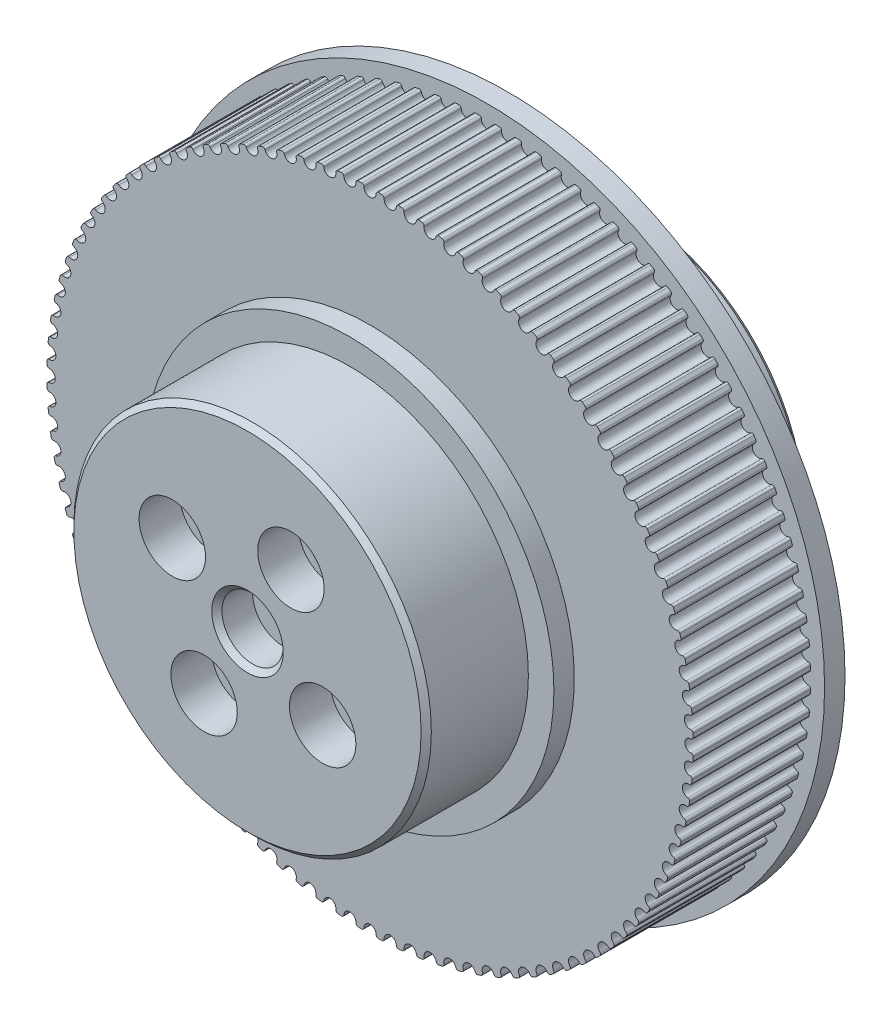
SolidWorks part; units mm, degrees
note: '?' marks a value the reader was unsure of.
ref_plane "Спереди" through (0, 0, 0) normal (0, 0, 1) x (1, 0, 0)
ref_plane "Сверху" through (0, 0, 0) normal (0, 1, 0) x (1, 0, 0)
ref_plane "Справа" through (0, 0, 0) normal (1, 0, 0) x (0, 0, -1)
ref_axis "Ось1" through (0, 0, 55) along (0, 0, -1)?
sketch "SketchRevolveGearBelt01" plane through (0, 0, 0) normal (1, 0, 0) x (0, 0, -1)
  line L0 (0, 0) -> (11.5, 0)
  line L1 (11.5, 0) -> (11.5, 31.6405)
  line L2 (11.5, 31.6405) -> (0, 31.6405)
  line L3 (0, 31.6405) -> (0, 0)
  dimension "GearBeltOutsideDiameter" = 31.6405
  dimension "D1" = 11.5
revolve "GearBelt01" add sketch "SketchRevolveGearBelt01" angle 360 about L0
sketch "SketchToothGearBelt01" plane through (0, 0, 0) normal (0, 0, 1) x (1, 0, 0)
  line L0 (-0.814, 31.63) -> (0, 34.1805)
  line L1 (0, 34.1805) -> (0.814, 31.63)
  arc A0 (0.814, 31.63) -> (0.6, 31.4215) centre (0.8086, 31.4215) ccw
  arc A1 (0.6, 31.4215) -> (-0.6, 31.4215) centre (0, 31.4215) cw
  arc A2 (-0.6, 31.4215) -> (-0.814, 31.63) centre (-0.8086, 31.4215) ccw
  dimension "GearBeltToothR1" = 0.4172
  dimension "GearBeltToothR2" = 1.2
  dimension "GearBeltToothCapX1" = 0.814
  dimension "GearBeltToothCapY1" = 2.5505
  dimension "GearBeltToothCapX2" = 0.814
  dimension "GearBeltToothCapY2" = 2.5505
extrude "ToothExtrudeCutGearBelt01" cut sketch "SketchToothGearBelt01" against normal blind 11.5
ref_axis "Ось2" through (34.8045, 0, 0) along (-1, 0, 0)?
ref_plane "Плоскость1" through (0, 0, 0) normal (0, 0, -1) x (1, 0, 0)
pattern_circular "PatternGearBelt01" count 100 every 3.6 about axis through (0, 0, 0) along (0, 0, 1) of "ToothExtrudeCutGearBelt01"
sketch "Эскиз5" plane through (0, 0, 0) normal (0, 0, -1) x (-1, 0, 0)
  circle A0 centre (0, 0) radius 33
  dimension "D1" = 66
extrude "Бобышка-Вытянуть1" [suppressed] add sketch "Эскиз5" against normal blind 2
sketch "Эскиз20" plane through (0, 0, -11.5) normal (0, 0, -1) x (-1, 0, 0)
  circle A0 centre (0, 0) radius 33
  dimension "D1" = 66
extrude "Бобышка-Вытянуть10" add sketch "Эскиз20" along normal blind 2
sketch "Эскиз12" plane through (0, 0, -13.5) normal (0, 0, -1) x (-1, 0, 0)
  circle A0 centre (0, 0) radius 20
extrude "Бобышка-Вытянуть5" add sketch "Эскиз12" along normal blind 2
sketch "Эскиз6" plane through (0, 0, 0) normal (0, 0, 1) x (1, 0, 0)
  circle A0 centre (0, 0) radius 20
  dimension "D1" = 40
extrude "Бобышка-Вытянуть6" add sketch "Эскиз6" along normal blind 2
sketch "Эскиз13" plane through (0, 0, 2) normal (0, 0, 1) x (1, 0, 0)
  circle A0 centre (0, 0) radius 17.5
  dimension "D1" = 35
extrude "Бобышка-Вытянуть7" add sketch "Эскиз13" along normal blind 10
sketch "Эскиз14" plane through (0, 0, -15.5) normal (0, 0, -1) x (-1, 0, 0)
  circle A0 centre (0, 0) radius 17.5
  dimension "D1" = 35
extrude "Бобышка-Вытянуть8" add sketch "Эскиз14" along normal blind 10
sketch "Эскиз15" plane through (0, 0, -25.5) normal (0, 0, -1) x (-1, 0, 0)
  circle A0 centre (0, 0) radius 12.1
  dimension "D1" = 24.2
extrude "Вырез-Вытянуть1" cut sketch "Эскиз15" against normal blind 7
sketch "Эскиз16" plane through (0, 0, 0) normal (0, 0, 1) x (1, 0, 0)
  line L0 (0, 0) -> (4.25, 7.3612) construction
  line L1 (0, 0) -> (-46.2056, 0) construction
  line L2 (0, 0) -> (7.3612, -4.25) construction
  line L3 (0, 0) -> (-4.25, -7.3612) construction
  line L4 (0, 0) -> (-7.3612, 4.25) construction
  circle A0 centre (0, 0) radius 8.5 construction
  circle A1 centre (4.25, 7.3612) radius 1.75
  circle A2 centre (7.3612, -4.25) radius 1.75
  circle A3 centre (-4.25, -7.3612) radius 1.75
  circle A4 centre (-7.3612, 4.25) radius 1.75
  point P16 (0, 0)
  dimension "D1" = 17
  dimension "D3" = 3.5
  dimension "D2" = 60
  dimension "D4" = 4
extrude "Вырез-Вытянуть2" cut sketch "Эскиз16" against normal through all both and the other way through all
sketch "Эскиз17" plane through (0, 0, 12) normal (0, 0, 1) x (1, 0, 0)
  circle A0 centre (4.25, 7.3612) radius 3.25
  circle A1 centre (7.3612, -4.25) radius 3.25
  circle A2 centre (-4.25, -7.3612) radius 3.25
  circle A3 centre (-7.3612, 4.25) radius 3.25
  point P12 (0, 0)
  dimension "D1" = 4
extrude "Вырез-Вытянуть3" cut sketch "Эскиз17" against normal blind 4
sketch "Эскиз18" plane through (0, 0, 12) normal (0, 0, 1) x (1, 0, 0)
  circle A0 centre (0, 0) radius 3
extrude "Вырез-Вытянуть4" cut sketch "Эскиз18" against normal blind 3.5
sketch "Эскиз19" plane through (0, 0, 0) normal (0, 0, 1) x (1, 0, 0)
  circle A0 centre (0, 0) radius 1
extrude "Вырез-Вытянуть5" cut sketch "Эскиз19" against normal through all both and the other way through all
chamfer "Фаска1" distance 0.5 angle 45 3 edges at (-12.1, 0, -25.5) (-17.5, 0, -25.5) (17.5, 0, 12)
fillet "Скругление1" radius 0.4 1 edges at (-12.1, 0, -18.5)
chamfer "Фаска2" distance 0.5 angle 45 1 edges at (3, 0, 12)
chamfer "Фаска3" [suppressed] distance 0.5 angle 45
